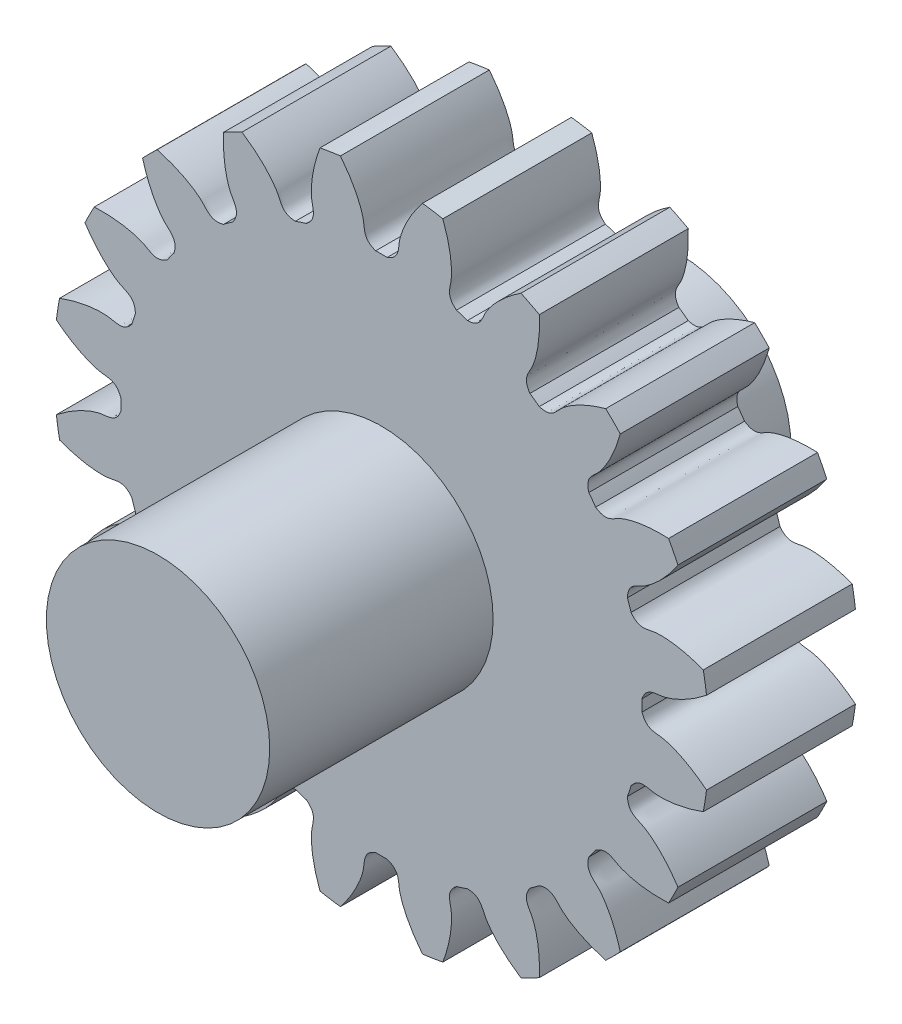
SolidWorks part; units mm, degrees
ref_plane "前视基准面" through (0, 0, 0) normal (0, 0, 1) x (1, 0, 0)
ref_plane "上视基准面" through (0, 0, 0) normal (0, 1, 0) x (1, 0, 0)
ref_plane "右视基准面" through (0, 0, 0) normal (1, 0, 0) x (0, 0, -1)
sketch "草图1" plane through (0, 0, 0) normal (0, 0, 1) x (1, 0, 0)
  circle A0 centre (0, 0) radius 22
extrude "凸台-拉伸1" add sketch "草图1" along normal blind 10
ref_axis "基准轴1" through (0, 0, 10) along (0, 0, -1)
sketch "草图2" plane through (0, 0, 0) normal (0, 0, 1) x (1, 0, 0)
  line L0 (0, 0) -> (0, 22) construction
  circle A0 centre (0, 0) radius 22 construction
  arc A1 (0.3866, 17.4957) -> (-0.3866, 17.4957) centre (0, 0) ccw
  arc A2 (6.3623, 24.9965) -> (-6.3623, 24.9965) centre (0, 0) ccw
  spline S0 degree 3 poles (0.3866, 17.4957) (1.2224, 17.787) (1.1142, 18.3742) (1.2258, 18.94) (1.2378, 18.9951) (1.2526, 19.0573) (1.2706, 19.1264) (1.292, 19.2024) (1.317, 19.2851) (1.3461, 19.3745) (1.3793, 19.4704) (1.4171, 19.5726) (1.4597, 19.6811) (1.5073, 19.7956) (1.5603, 19.9161) (1.6187, 20.0423) (1.683, 20.174) (1.7534, 20.3112) (1.83, 20.4535) (1.9132, 20.6008) (2.0031, 20.7529) (2.1, 20.9095) (2.204, 21.0705) (2.3155, 21.2356) (2.4346, 21.4046) (2.5615, 21.5772) (2.6964, 21.7533) (2.8395, 21.9324) (2.991, 22.1145) (3.1509, 22.2992) (3.3196, 22.4862) (3.4971, 22.6753) (3.6837, 22.8662) (3.8793, 23.0586) (4.0843, 23.2521) (4.2986, 23.4467) (4.5225, 23.6418) (4.7559, 23.8372) (4.9991, 24.0327) (5.2521, 24.2278) (5.515, 24.4223) (5.8829, 24.6833) (6.1679, 24.8727) (6.3623, 24.9965) knots 0 0 0 0 0.165916 0.170906 0.176664 0.183189 0.190482 0.198542 0.207371 0.216967 0.22733 0.238462 0.250361 0.263027 0.276462 0.290664 0.305634 0.321371 0.337876 0.355149 0.37319 0.391998 0.411574 0.431917 0.453028 0.474907 0.497554 0.520968 0.54515 0.570099 0.595817 0.622302 0.649554 0.677575 0.706363 0.735918 0.766242 0.797333 0.829191 0.861818 0.895212 0.929373 1 1 1 1
  spline S1 degree 3 poles (-0.3866, 17.4957) (-1.2224, 17.787) (-1.1142, 18.3742) (-1.2258, 18.94) (-1.2378, 18.9951) (-1.2526, 19.0573) (-1.2706, 19.1264) (-1.292, 19.2024) (-1.317, 19.2851) (-1.3461, 19.3745) (-1.3793, 19.4704) (-1.4171, 19.5726) (-1.4597, 19.6811) (-1.5073, 19.7956) (-1.5603, 19.9161) (-1.6187, 20.0423) (-1.683, 20.174) (-1.7534, 20.3112) (-1.83, 20.4535) (-1.9132, 20.6008) (-2.0031, 20.7529) (-2.1, 20.9095) (-2.204, 21.0705) (-2.3155, 21.2356) (-2.4346, 21.4046) (-2.5615, 21.5772) (-2.6964, 21.7533) (-2.8395, 21.9324) (-2.991, 22.1145) (-3.1509, 22.2992) (-3.3196, 22.4862) (-3.4971, 22.6753) (-3.6837, 22.8662) (-3.8793, 23.0586) (-4.0843, 23.2521) (-4.2986, 23.4467) (-4.5225, 23.6418) (-4.7559, 23.8372) (-4.9991, 24.0327) (-5.2521, 24.2278) (-5.515, 24.4223) (-5.8829, 24.6833) (-6.1679, 24.8727) (-6.3623, 24.9965) knots 0 0 0 0 0.165916 0.170906 0.176664 0.183189 0.190482 0.198542 0.207371 0.216967 0.22733 0.238462 0.250361 0.263027 0.276462 0.290664 0.305634 0.321371 0.337876 0.355149 0.37319 0.391998 0.411574 0.431917 0.453028 0.474907 0.497554 0.520968 0.54515 0.570099 0.595817 0.622302 0.649554 0.677575 0.706363 0.735918 0.766242 0.797333 0.829191 0.861818 0.895212 0.929373 1 1 1 1
extrude "切除-拉伸1" cut sketch "草图2" along normal through all
pattern_circular "阵列(圆周)1" count 20 every 18 about axis through (0, 0, 10) along (0, 0, -1) of "切除-拉伸1"
sketch "草图3" plane through (0, 0, 0) normal (0, 0, 1) x (1, 0, 0)
  circle A0 centre (0, 0) radius 20 construction
  dimension "Dn" = 40
sketch "草图4" plane through (0, 0, 10) normal (0, 0, 1) x (1, 0, 0)
  circle A0 centre (0, 0) radius 7.5
  dimension "D1" = 15
sketch "草图5" plane through (0, 0, 10) normal (0, 0, 1) x (1, 0, 0)
  circle A0 centre (0, 0) radius 20 construction
  dimension "D1" = 40
extrude "凸台-拉伸2" add sketch "草图4" along normal blind 15
sketch "草图6" plane through (0, 0, 0) normal (0, 0, -1) x (-1, 0, 0)
  circle A0 centre (0, 0) radius 7.5
  dimension "D1" = 15
extrude "凸台-拉伸3" add sketch "草图6" along normal blind 10
